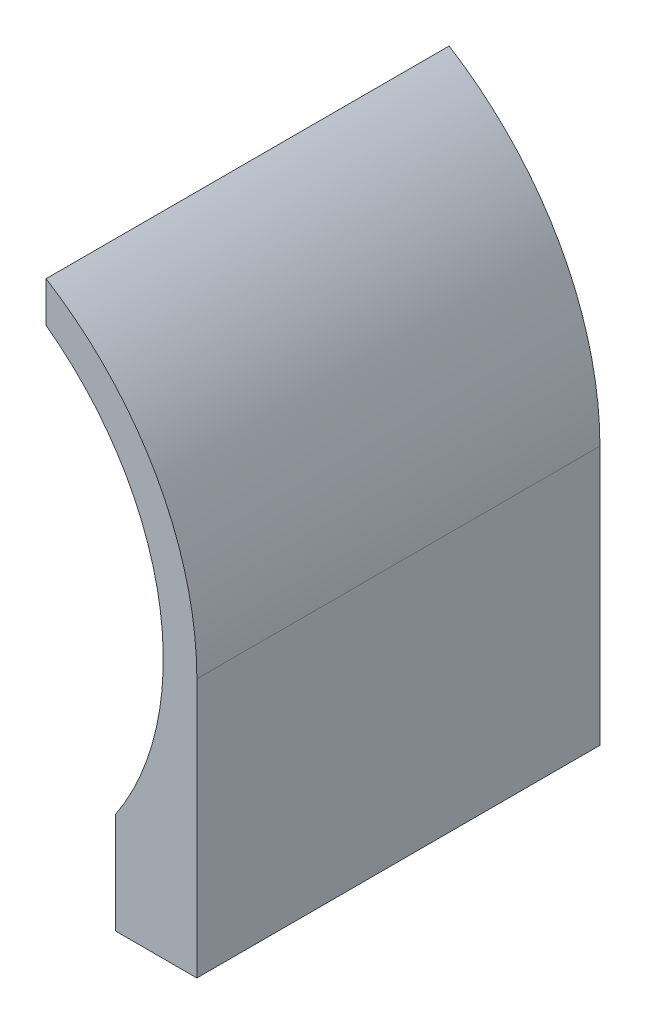
SolidWorks part; units mm, degrees
ref_plane "Front Plane" through (0, 0, 0) normal (0, 0, 1) x (1, 0, 0)
ref_plane "Top Plane" through (0, 0, 0) normal (0, 1, 0) x (1, 0, 0)
ref_plane "Right Plane" through (0, 0, 0) normal (1, 0, 0) x (0, 0, -1)
sketch "Sketch2" plane through (0, 0, 0) normal (0, 0, 1) x (1, 0, 0)
  line L0 (-81.7487, 0) -> (129.7647, 0) construction
  line L1 (0, 82.2046) -> (0, -80.6851) construction
  line L2 (50.1, 0) -> (50.1, 106.5165) construction
  line L3 (-70.7312, -47.1391) -> (70.7312, -47.1391) construction
  line L4 (70.7312, -47.1391) -> (70.7312, -77.1391)
  line L5 (95, 0) -> (95, -77.1391)
  line L6 (95, -77.1391) -> (70.7312, -77.1391)
  line L7 (50.1, 80.7155) -> (50.1, 68.6658)
  circle A0 centre (0, 0) radius 85 construction
  circle A1 centre (0, 0) radius 95 construction
  arc A2 (50.1, 68.6658) -> (70.7312, -47.1391) centre (0, 0) cw
  arc A3 (95, 0) -> (50.1, 80.7155) centre (0, 0) ccw
  point P18 (69.3935, -49.0871)
  dimension "D1" = 170
  dimension "D2" = 190
  dimension "D3" = 50.1
  dimension "D4" = 167.1
  dimension "D5" = 30
extrude "Inner Ring - Right Side" add sketch "Sketch2" along normal blind 120
